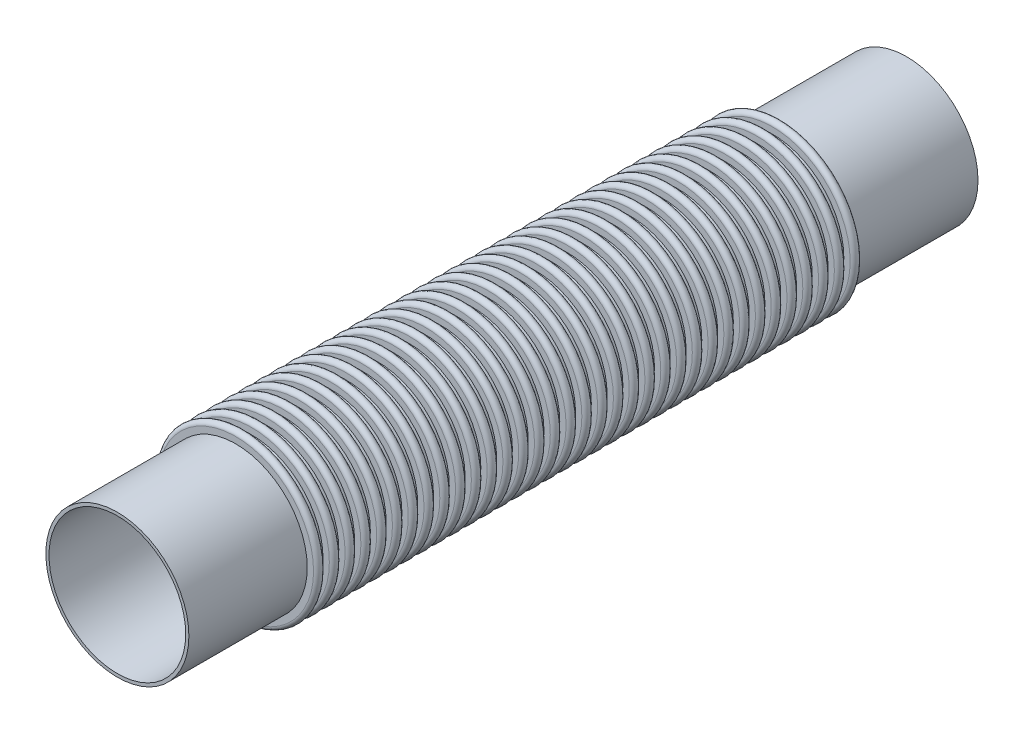
SolidWorks part; units mm, degrees
material "PE High Density"
ref_plane "Front" through (0, 0, 0) normal (0, 0, 1) x (1, 0, 0)
ref_plane "Top" through (0, 0, 0) normal (0, 1, 0) x (1, 0, 0)
ref_plane "Right" through (0, 0, 0) normal (1, 0, 0) x (0, 0, -1)
ref_axis "Axis1" through (0, 0, 55) along (0, 0, -1)
sketch "Sketch1" plane through (0, 0, 0) normal (1, 0, 0) x (0, 0, -1)
  line L0 (-63.5, 0) -> (63.5, 0) construction
  line L1 (-63.5, 0) -> (-63.5, 11.508) construction
  line L2 (63.5, 0) -> (63.5, 17.6062) construction
  line L3 (-63.5, 11) -> (-44.45, 11)
  line L4 (0, 0) -> (0, 11) construction
  line L5 (-63.5, 11.508) -> (-44.45, 11.508)
  line L6 (-44.45, 11.508) -> (-44.45, 12.524)
  line L7 (63.5, 11) -> (44.45, 11)
  line L8 (-43.18, 12.524) -> (-43.18, 11.508)
  line L9 (-43.18, 11.508) -> (-41.91, 11.508)
  line L10 (63.5, 11.508) -> (44.45, 11.508)
  line L11 (-63.5, 11.508) -> (-63.5, 11)
  line L12 (63.5, 11.508) -> (63.5, 11)
  line L13 (-41.91, 11.508) -> (-41.91, 12.524)
  line L14 (-40.64, 12.524) -> (-40.64, 11.508)
  line L15 (-40.64, 11.508) -> (-39.37, 11.508)
  line L16 (-39.37, 11.508) -> (-39.37, 12.524)
  line L17 (-38.1, 12.524) -> (-38.1, 11.508)
  line L18 (-38.1, 11.508) -> (-36.83, 11.508)
  line L19 (-36.83, 11.508) -> (-36.83, 12.524)
  line L20 (-35.56, 12.524) -> (-35.56, 11.508)
  line L21 (-35.56, 11.508) -> (-34.29, 11.508)
  line L22 (-34.29, 11.508) -> (-34.29, 12.524)
  line L23 (-33.02, 12.524) -> (-33.02, 11.508)
  line L24 (-33.02, 11.508) -> (-31.75, 11.508)
  line L25 (-31.75, 11.508) -> (-31.75, 12.524)
  line L26 (-30.48, 12.524) -> (-30.48, 11.508)
  line L27 (-30.48, 11.508) -> (-29.21, 11.508)
  line L28 (-29.21, 11.508) -> (-29.21, 12.524)
  line L29 (-27.94, 12.524) -> (-27.94, 11.508)
  line L30 (-27.94, 11.508) -> (-26.67, 11.508)
  line L31 (-26.67, 11.508) -> (-26.67, 12.524)
  line L32 (-25.4, 12.524) -> (-25.4, 11.508)
  line L33 (-25.4, 11.508) -> (-24.13, 11.508)
  line L34 (-24.13, 11.508) -> (-24.13, 12.524)
  line L35 (-22.86, 12.524) -> (-22.86, 11.508)
  line L36 (-22.86, 11.508) -> (-21.59, 11.508)
  line L37 (-21.59, 11.508) -> (-21.59, 12.524)
  line L38 (-20.32, 12.524) -> (-20.32, 11.508)
  line L39 (-20.32, 11.508) -> (-19.05, 11.508)
  line L40 (-19.05, 11.508) -> (-19.05, 12.524)
  line L41 (-17.78, 12.524) -> (-17.78, 11.508)
  line L42 (-17.78, 11.508) -> (-16.51, 11.508)
  line L43 (-16.51, 11.508) -> (-16.51, 12.524)
  line L44 (-15.24, 12.524) -> (-15.24, 11.508)
  line L45 (-15.24, 11.508) -> (-13.97, 11.508)
  line L46 (-13.97, 11.508) -> (-13.97, 12.524)
  line L47 (-12.7, 12.524) -> (-12.7, 11.508)
  line L48 (-12.7, 11.508) -> (-11.43, 11.508)
  line L49 (-11.43, 11.508) -> (-11.43, 12.524)
  line L50 (-10.16, 12.524) -> (-10.16, 11.508)
  line L51 (-10.16, 11.508) -> (-8.89, 11.508)
  line L52 (-8.89, 11.508) -> (-8.89, 12.524)
  line L53 (-7.62, 12.524) -> (-7.62, 11.508)
  line L54 (-7.62, 11.508) -> (-6.35, 11.508)
  line L55 (-6.35, 11.508) -> (-6.35, 12.524)
  line L56 (-5.08, 12.524) -> (-5.08, 11.508)
  line L57 (-5.08, 11.508) -> (-3.81, 11.508)
  line L58 (-3.81, 11.508) -> (-3.81, 12.524)
  line L59 (-2.54, 12.524) -> (-2.54, 11.508)
  line L60 (-2.54, 11.508) -> (-1.27, 11.508)
  line L61 (-1.27, 11.508) -> (-1.27, 12.524)
  line L62 (0, 12.524) -> (0, 11.508)
  line L63 (0, 11.508) -> (1.27, 11.508)
  line L64 (1.27, 11.508) -> (1.27, 12.524)
  line L65 (2.54, 12.524) -> (2.54, 11.508)
  line L66 (2.54, 11.508) -> (3.81, 11.508)
  line L67 (3.81, 11.508) -> (3.81, 12.524)
  line L68 (5.08, 12.524) -> (5.08, 11.508)
  line L69 (5.08, 11.508) -> (6.35, 11.508)
  line L70 (6.35, 11.508) -> (6.35, 12.524)
  line L71 (7.62, 12.524) -> (7.62, 11.508)
  line L72 (7.62, 11.508) -> (8.89, 11.508)
  line L73 (8.89, 11.508) -> (8.89, 12.524)
  line L74 (10.16, 12.524) -> (10.16, 11.508)
  line L75 (10.16, 11.508) -> (11.43, 11.508)
  line L76 (11.43, 11.508) -> (11.43, 12.524)
  line L77 (12.7, 12.524) -> (12.7, 11.508)
  line L78 (12.7, 11.508) -> (13.97, 11.508)
  line L79 (13.97, 11.508) -> (13.97, 12.524)
  line L80 (15.24, 12.524) -> (15.24, 11.508)
  line L81 (15.24, 11.508) -> (16.51, 11.508)
  line L82 (16.51, 11.508) -> (16.51, 12.524)
  line L83 (17.78, 12.524) -> (17.78, 11.508)
  line L84 (17.78, 11.508) -> (19.05, 11.508)
  line L85 (19.05, 11.508) -> (19.05, 12.524)
  line L86 (20.32, 12.524) -> (20.32, 11.508)
  line L87 (20.32, 11.508) -> (21.59, 11.508)
  line L88 (21.59, 11.508) -> (21.59, 12.524)
  line L89 (22.86, 12.524) -> (22.86, 11.508)
  line L90 (22.86, 11.508) -> (24.13, 11.508)
  line L91 (24.13, 11.508) -> (24.13, 12.524)
  line L92 (25.4, 12.524) -> (25.4, 11.508)
  line L93 (25.4, 11.508) -> (26.67, 11.508)
  line L94 (26.67, 11.508) -> (26.67, 12.524)
  line L95 (27.94, 12.524) -> (27.94, 11.508)
  line L96 (27.94, 11.508) -> (29.21, 11.508)
  line L97 (29.21, 11.508) -> (29.21, 12.524)
  line L98 (30.48, 12.524) -> (30.48, 11.508)
  line L99 (30.48, 11.508) -> (31.75, 11.508)
  line L100 (-44.45, 11) -> (44.45, 11)
  line L101 (31.75, 11.508) -> (31.75, 12.524)
  line L102 (33.02, 12.524) -> (33.02, 11.508)
  line L103 (33.02, 11.508) -> (34.29, 11.508)
  line L104 (34.29, 11.508) -> (34.29, 12.524)
  line L105 (35.56, 12.524) -> (35.56, 11.508)
  line L106 (35.56, 11.508) -> (36.83, 11.508)
  line L107 (36.83, 11.508) -> (36.83, 12.524)
  line L108 (38.1, 12.524) -> (38.1, 11.508)
  line L109 (38.1, 11.508) -> (39.37, 11.508)
  line L110 (39.37, 11.508) -> (39.37, 12.524)
  line L111 (40.64, 12.524) -> (40.64, 11.508)
  line L112 (40.64, 11.508) -> (41.91, 11.508)
  line L113 (41.91, 11.508) -> (41.91, 12.524)
  line L114 (43.18, 12.524) -> (43.18, 11.508)
  line L115 (43.18, 11.508) -> (44.45, 11.508)
  arc A0 (-44.45, 12.524) -> (-43.18, 12.524) centre (-43.815, 12.524) cw
  arc A1 (-41.91, 12.524) -> (-40.64, 12.524) centre (-41.275, 12.524) cw
  arc A2 (-39.37, 12.524) -> (-38.1, 12.524) centre (-38.735, 12.524) cw
  arc A3 (-36.83, 12.524) -> (-35.56, 12.524) centre (-36.195, 12.524) cw
  arc A4 (-34.29, 12.524) -> (-33.02, 12.524) centre (-33.655, 12.524) cw
  arc A5 (-31.75, 12.524) -> (-30.48, 12.524) centre (-31.115, 12.524) cw
  arc A6 (-29.21, 12.524) -> (-27.94, 12.524) centre (-28.575, 12.524) cw
  arc A7 (-26.67, 12.524) -> (-25.4, 12.524) centre (-26.035, 12.524) cw
  arc A8 (-24.13, 12.524) -> (-22.86, 12.524) centre (-23.495, 12.524) cw
  arc A9 (-21.59, 12.524) -> (-20.32, 12.524) centre (-20.955, 12.524) cw
  arc A10 (-19.05, 12.524) -> (-17.78, 12.524) centre (-18.415, 12.524) cw
  arc A11 (-16.51, 12.524) -> (-15.24, 12.524) centre (-15.875, 12.524) cw
  arc A12 (-13.97, 12.524) -> (-12.7, 12.524) centre (-13.335, 12.524) cw
  arc A13 (-11.43, 12.524) -> (-10.16, 12.524) centre (-10.795, 12.524) cw
  arc A14 (-8.89, 12.524) -> (-7.62, 12.524) centre (-8.255, 12.524) cw
  arc A15 (-6.35, 12.524) -> (-5.08, 12.524) centre (-5.715, 12.524) cw
  arc A16 (-3.81, 12.524) -> (-2.54, 12.524) centre (-3.175, 12.524) cw
  arc A17 (-1.27, 12.524) -> (0, 12.524) centre (-0.635, 12.524) cw
  arc A18 (1.27, 12.524) -> (2.54, 12.524) centre (1.905, 12.524) cw
  arc A19 (3.81, 12.524) -> (5.08, 12.524) centre (4.445, 12.524) cw
  arc A20 (6.35, 12.524) -> (7.62, 12.524) centre (6.985, 12.524) cw
  arc A21 (8.89, 12.524) -> (10.16, 12.524) centre (9.525, 12.524) cw
  arc A22 (11.43, 12.524) -> (12.7, 12.524) centre (12.065, 12.524) cw
  arc A23 (13.97, 12.524) -> (15.24, 12.524) centre (14.605, 12.524) cw
  arc A24 (16.51, 12.524) -> (17.78, 12.524) centre (17.145, 12.524) cw
  arc A25 (19.05, 12.524) -> (20.32, 12.524) centre (19.685, 12.524) cw
  arc A26 (21.59, 12.524) -> (22.86, 12.524) centre (22.225, 12.524) cw
  arc A27 (24.13, 12.524) -> (25.4, 12.524) centre (24.765, 12.524) cw
  arc A28 (26.67, 12.524) -> (27.94, 12.524) centre (27.305, 12.524) cw
  arc A29 (29.21, 12.524) -> (30.48, 12.524) centre (29.845, 12.524) cw
  arc A30 (31.75, 12.524) -> (33.02, 12.524) centre (32.385, 12.524) cw
  arc A31 (34.29, 12.524) -> (35.56, 12.524) centre (34.925, 12.524) cw
  arc A32 (36.83, 12.524) -> (38.1, 12.524) centre (37.465, 12.524) cw
  arc A33 (39.37, 12.524) -> (40.64, 12.524) centre (40.005, 12.524) cw
  arc A34 (41.91, 12.524) -> (43.18, 12.524) centre (42.545, 12.524) cw
  point P4 (0, 0)
  dimension "D1" = 127
  dimension "D2" = 19.05
  dimension "D3" = 0.508
  dimension "D4" = 1.016
  dimension "D5" = 1.27
  dimension "D6" = 1.27
  dimension "D7" = 11
  dimension "D8" = 30
  dimension "D9" = 6
revolve "Revolve1" add sketch "Sketch1" angle 360 about L0 region at (0, 11.7739, 0.3243)
